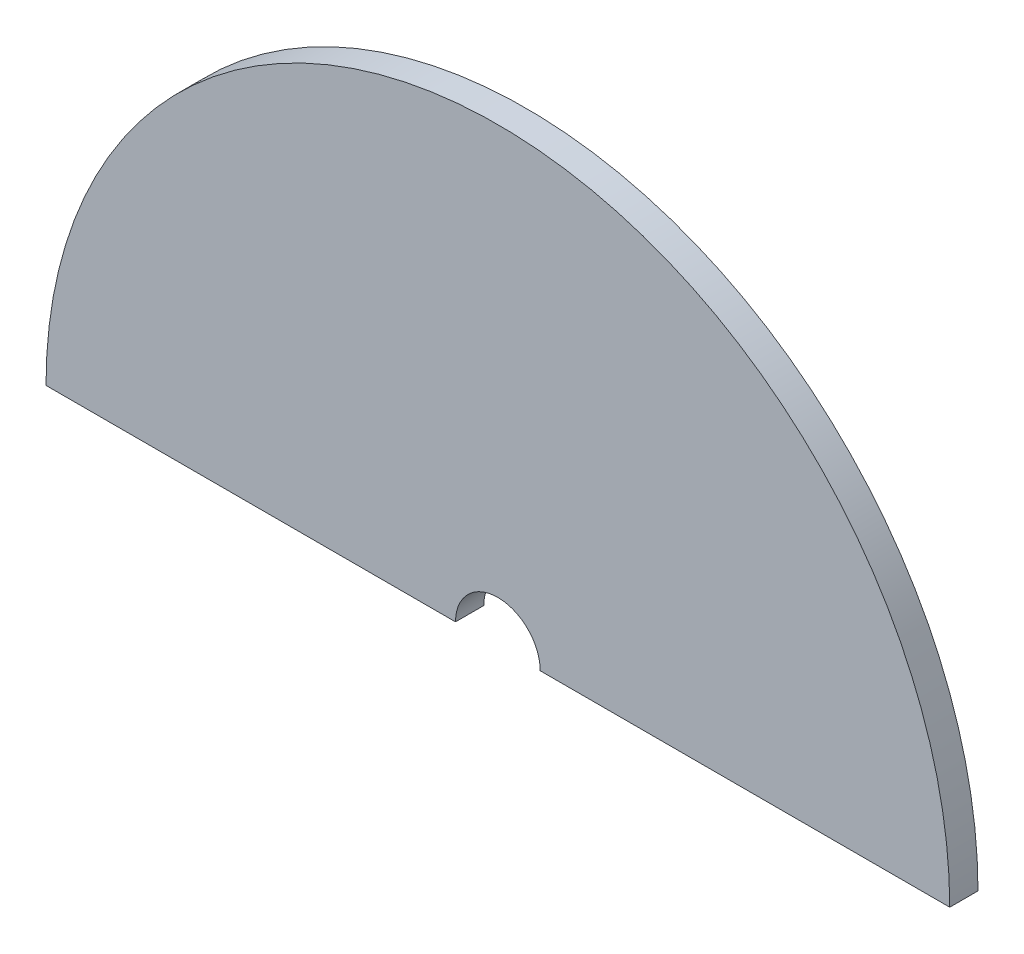
SolidWorks part; units mm, degrees
material "201 Annealed Stainless Steel (SS)"
ref_plane "Front Plane" through (0, 0, 0) normal (0, 0, 1) x (1, 0, 0)
ref_plane "Top Plane" through (0, 0, 0) normal (0, 1, 0) x (1, 0, 0)
ref_plane "Right Plane" through (0, 0, 0) normal (1, 0, 0) x (0, 0, -1)
sketch "Plate shape" plane through (0, 0, 0) normal (0, 0, 1) x (1, 0, 0)
  line L3 (-154.3999, 0) -> (210.7061, 0) construction
  line L4 (0, 160) -> (-160, 160)
  line L5 (0, 160) -> (160, 160)
  line L9 (0, 160) -> (0, 0) construction
  arc A0 (-160, 160) -> (160, 160) centre (0, 160) cw
  arc A1 (160, 160) -> (-160, 160) centre (0, 160) cw construction
  dimension "D1" = 160
extrude "Outer casing" add sketch "Plate shape" along normal blind 10
sketch "Sketch1" plane through (0, 0, 10) normal (0, 0, 1) x (1, 0, 0)
  circle A0 centre (0, 160) radius 160 construction
  arc A1 (160, 160) -> (-160, 160) centre (0, 160) ccw construction
  circle A2 centre (0, 160) radius 15
  dimension "D1" = 30
extrude "Inner Cutout" cut sketch "Sketch1" against normal blind 20
